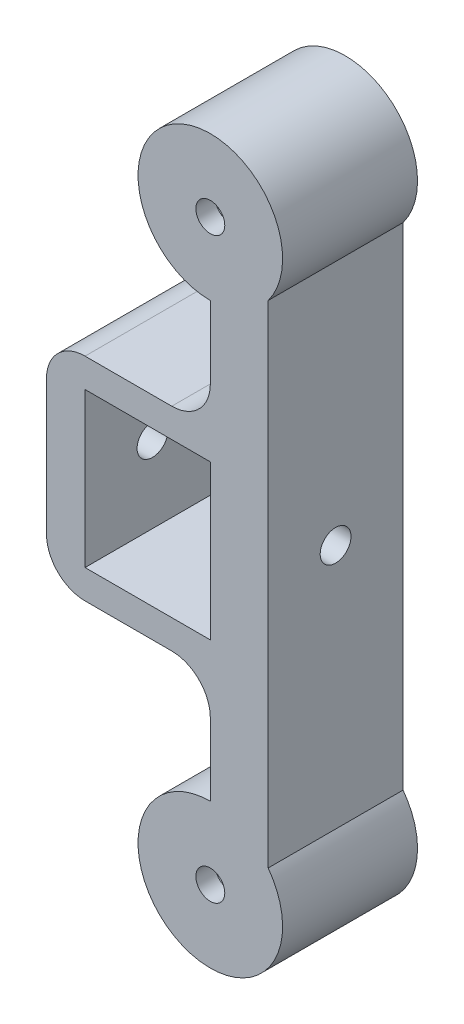
SolidWorks part; units mm, degrees
material "ABS"
ref_plane "Plano frontal" through (0, 0, 0) normal (0, 0, 1) x (1, 0, 0)
ref_plane "Plano superior" through (0, 0, 0) normal (0, 1, 0) x (1, 0, 0)
ref_plane "Plano direito" through (0, 0, 0) normal (1, 0, 0) x (0, 0, -1)
sketch "Esboço1" plane through (0, 0, 0) normal (0, 0, 1) x (1, 0, 0)
  line L0 (6, 55.5) -> (6, 4.5)
  line L2 (0, 41) -> (-17, 41)
  line L3 (-17, 41) -> (-17, 19)
  line L4 (-17, 19) -> (0, 19)
  line L5 (0, 22) -> (-13, 22)
  line L6 (-13, 22) -> (-13, 38)
  line L7 (0, 52.5) -> (0, 41)
  line L8 (-13, 38) -> (0, 38)
  line L10 (0, 19) -> (0, 7.5)
  line L11 (0, 38) -> (0, 22)
  circle A0 centre (0, 60) radius 4
  circle A1 centre (0, 0) radius 4
  arc A2 (6, 55.5) -> (0, 52.5) centre (0, 60) ccw
  arc A3 (0, 7.5) -> (6, 4.5) centre (0, 0) ccw
  point P15 (-13, 30)
  point P18 (6, 30)
  point P19 (0, 0)
  point P20 (0, 0)
  point P21 (-17, 30)
  dimension "D1" = 8
  dimension "D2" = 15
  dimension "D3" = 60
  dimension "D4" = 6
  dimension "D5" = 4
  dimension "D6" = 3
  dimension "D7" = 16
  dimension "D8" = 13
extrude "Ressalto-extrusão1" add sketch "Esboço1" along normal blind 14
sketch "Esboço3" plane through (0, 0, 14) normal (0, 0, 1) x (1, 0, 0)
  line L2 (0, 52.5) -> (0, 7.5)
  line L4 (6, 55.5) -> (6, 4.5)
  arc A0 (6, 55.5) -> (0, 52.5) centre (0, 60) ccw
  arc A1 (0, 7.5) -> (6, 4.5) centre (0, 0) ccw
  circle A2 centre (0, 60) radius 1.5
  circle A3 centre (0, 0) radius 1.5
  dimension "D1" = 3
extrude "Ressalto-extrusão2" add sketch "Esboço3" against normal blind 4
sketch "Esboço2" plane through (0, 0, 0) normal (-1, 0, 0) x (0, 0, 1)
  line L0 (0, 30) -> (14, 30) construction
  line L4 (0, 22) -> (0, 38) construction
  line L5 (14, 22) -> (14, 38) construction
  circle A0 centre (7, 30) radius 1.6
  point P2 (0, 30)
  point P3 (0, 30)
  point P5 (14, 30)
  point P10 (18, 30)
  dimension "D1" = 3.2
extrude "Corte-extrusão1" cut sketch "Esboço2" against normal through all both and the other way through all contours A0
sketch "Esboço4" plane through (0, 0, 14) normal (0, 0, 1) x (1, 0, 0)
  line L1 (0, 56.94) -> (2.65, 58.47)
  line L2 (2.65, 58.47) -> (2.65, 61.53)
  line L3 (2.65, 61.53) -> (0, 63.06)
  line L4 (0, 63.06) -> (-2.65, 61.53)
  line L5 (-2.65, 61.53) -> (-2.65, 58.47)
  line L6 (-2.65, 58.47) -> (0, 56.94)
  line L7 (0, -3.06) -> (2.65, -1.53)
  line L8 (2.65, -1.53) -> (2.65, 1.53)
  line L9 (2.65, 1.53) -> (0, 3.06)
  line L10 (0, 3.06) -> (-2.65, 1.53)
  line L11 (-2.65, 1.53) -> (-2.65, -1.53)
  line L12 (-2.65, -1.53) -> (0, -3.06)
  circle A0 centre (0, 60) radius 2.65 construction
  circle A1 centre (0, 0) radius 2.65 construction
  point P1 (0, 0)
  dimension "D1" = 5.3
extrude "Corte-extrusão2" cut sketch "Esboço4" against normal blind 2 from offset 2 offset against normal yes
fillet "Filete1" radius 4 4 edges at (0, 41, 7) (0, 19, 7) (-17, 19, 7) (-17, 41, 7)
